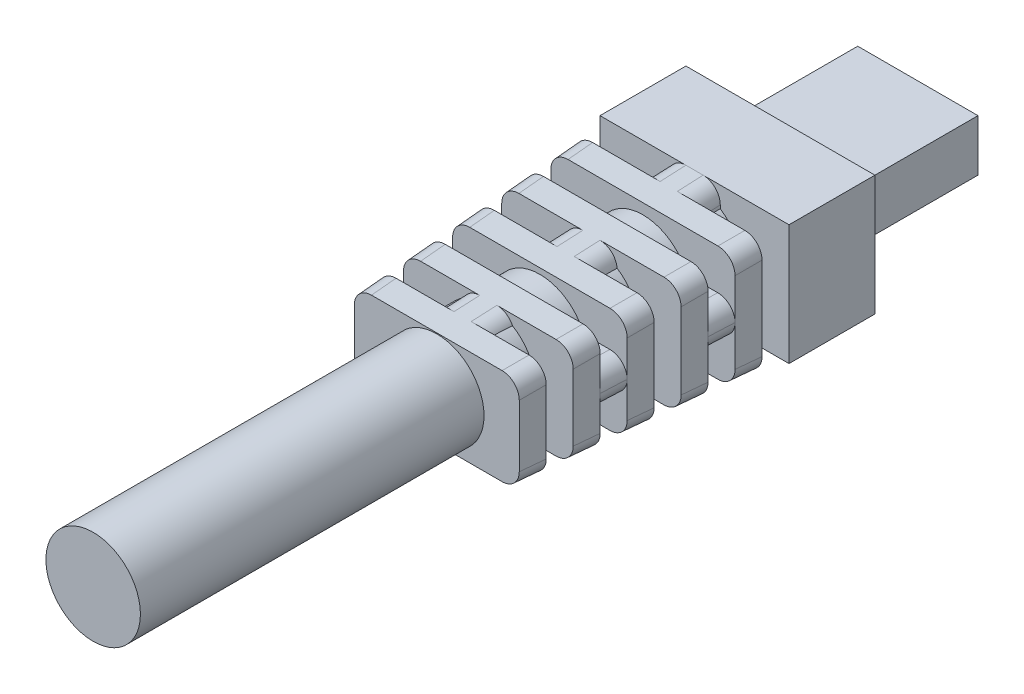
SolidWorks part; units mm, degrees
material "ПВХ 0.007 Смягченный"
ref_plane "Front" through (0, 0, 0) normal (0, 0, 1) x (1, 0, 0)
ref_plane "Top" through (0, 0, 0) normal (0, 1, 0) x (1, 0, 0)
ref_plane "Right" through (0, 0, 0) normal (1, 0, 0) x (0, 0, -1)
sketch "Эскиз1" plane through (0, 0, 0) normal (0, 0, 1) x (1, 0, 0)
  line L1 (0, 0) -> (-7, 0)
  line L2 (0, 0) -> (0, 3)
  line L3 (0, 3) -> (-7, 3)
  line L4 (-7, 0) -> (-7, 3)
  dimension "D1" = 7
  dimension "D2" = 3
extrude "Бобышка-Вытянуть1" add sketch "Эскиз1" along normal blind 8
sketch "Эскиз2" plane through (0, 0, 8) normal (0, 0, 1) x (1, 0, 0)
  line L0 (-7, 3) -> (-7, 0) construction
  line L1 (-9, -2) -> (2, -2)
  line L2 (-9, -2) -> (-9, 5)
  line L3 (-9, 5) -> (2, 5)
  line L4 (2, -2) -> (2, 5)
  line L5 (0, 0) -> (0, 3) construction
  line L6 (0, 3) -> (-7, 3) construction
  line L7 (-7, 0) -> (0, 0) construction
  point P4 (-7, 1.5)
  point P7 (0, 1.5)
  point P10 (-3.5, 3)
  dimension "D1" = 2
  dimension "D2" = 2
  dimension "D3" = 2
  dimension "D4" = 2
extrude "Бобышка-Вытянуть2" add sketch "Эскиз2" along normal blind 5
sketch "Эскиз3" plane through (0, 0, 13) normal (0, 0, 1) x (1, 0, 0)
  line L1 (-9, -2) -> (2, -2)
  line L2 (-9, -2) -> (-9, 5)
  line L3 (-9, 5) -> (2, 5)
  line L4 (2, -2) -> (2, 5)
extrude "Бобышка-Вытянуть3" add sketch "Эскиз3" along normal blind 15
chamfer "Фаска1" distance 15 distance2 0.7 4 edges at (2, 1.5, 28) (-3.5, 5, 28) (-9, 1.5, 28) (-3.5, -2, 28) first distance on face at (2, 1.5, 18) first distance on face at (-3.5, 5, 18) first distance on face at (-9, 1.5, 18) first distance on face at (-3.5, -2, 18)
ref_plane "Плоскость1" through (-3.5, 0, 0) normal (-1, 0, 0) x (0, 0, 1)
sketch "Эскиз5" plane through (-9, 0, 0) normal (-1, 0, 0) x (0, 0, 1)
  line L0 (16, -2) -> (17.5, -2)
  line L1 (13, -2) -> (14.5, -2)
  line L2 (13, -2) -> (13, 0.5)
  line L3 (13, 0.5) -> (14.5, 0.5)
  line L4 (14.5, -2) -> (14.5, 0.5)
  line L5 (16, -2) -> (16, 0.5)
  line L6 (16, 0.5) -> (17.5, 0.5)
  line L7 (17.5, -2) -> (17.5, 0.5)
  line L8 (19, -2) -> (20.5, -2)
  line L9 (19, -2) -> (19, 0.5)
  line L10 (19, 0.5) -> (20.5, 0.5)
  line L11 (20.5, -2) -> (20.5, 0.5)
  line L12 (22, -2) -> (23.5, -2)
  line L13 (22, -2) -> (22, 0.5)
  line L14 (22, 0.5) -> (23.5, 0.5)
  line L15 (23.5, -2) -> (23.5, 0.5)
  line L16 (25, -2) -> (26.5, -2)
  line L17 (25, -2) -> (25, 0.5)
  line L18 (25, 0.5) -> (26.5, 0.5)
  line L19 (26.5, -2) -> (26.5, 0.5)
  line L20 (16, 2.5) -> (17.5, 2.5)
  line L21 (16, 2.5) -> (16, 5)
  line L22 (16, 5) -> (17.5, 5)
  line L23 (17.5, 2.5) -> (17.5, 5)
  line L24 (19, 2.5) -> (20.5, 2.5)
  line L25 (19, 2.5) -> (19, 5)
  line L26 (19, 5) -> (20.5, 5)
  line L27 (20.5, 2.5) -> (20.5, 5)
  line L28 (22, 2.5) -> (23.5, 2.5)
  line L29 (22, 2.5) -> (22, 5)
  line L30 (22, 5) -> (23.5, 5)
  line L31 (23.5, 2.5) -> (23.5, 5)
  line L32 (25, 2.5) -> (26.5, 2.5)
  line L33 (25, 2.5) -> (25, 5)
  line L34 (25, 5) -> (26.5, 5)
  line L35 (26.5, 2.5) -> (26.5, 5)
  line L36 (13, 2.5) -> (14.5, 2.5)
  line L37 (13, 2.5) -> (13, 5)
  line L38 (13, 5) -> (14.5, 5)
  line L39 (14.5, 2.5) -> (14.5, 5)
  dimension "D1" = 1.5
  dimension "D2" = 2.5
  dimension "D3" = 5
  dimension "D4" = 2
extrude "Вырез-Вытянуть1" cut sketch "Эскиз5" against normal blind 4
mirror "Зеркальное отражение1" about plane through (-3.5, 0, 0) normal (-1, 0, 0) of "Вырез-Вытянуть1"
fillet "Скругление1" radius 1 10 edges at (-8.335, -1.335, 27.25) (-8.475, -1.475, 24.25) (-8.615, -1.615, 21.25) (-8.755, -1.755, 18.25) (-8.895, -1.895, 15.25) (-8.335, 4.335, 27.25) (-8.475, 4.475, 24.25) (-8.615, 4.615, 21.25) (-8.755, 4.755, 18.25) (-8.895, 4.895, 15.25)
fillet "Скругление2" radius 1 10 edges at (1.895, -1.895, 15.25) (1.755, -1.755, 18.25) (1.615, -1.615, 21.25) (1.475, -1.475, 24.25) (1.335, -1.335, 27.25) (1.895, 4.895, 15.25) (1.755, 4.755, 18.25) (1.615, 4.615, 21.25) (1.475, 4.475, 24.25) (1.335, 4.335, 27.25)
sketch "Эскиз6" plane through (-9, 0, 0) normal (-1, 0, 0) x (0, 0, 1)
  line L0 (19, 0.5) -> (19, 2.5)
  line L1 (13, 0.5) -> (14.5, 0.5)
  line L2 (13, 0.5) -> (13, 2.5)
  line L3 (13, 2.5) -> (14.5, 2.5)
  line L4 (14.5, 0.5) -> (14.5, 2.5)
  line L5 (19, 0.5) -> (20.5, 0.5)
  line L6 (20.5, 0.5) -> (20.5, 2.5)
  line L7 (19, 2.5) -> (20.5, 2.5)
  line L8 (25, 0.5) -> (25, 2.5)
  line L9 (25, 0.5) -> (26.5, 0.5)
  line L10 (26.5, 0.5) -> (26.5, 2.5)
  line L11 (25, 2.5) -> (26.5, 2.5)
  dimension "D1" = 3
extrude "Вырез-Вытянуть2" cut sketch "Эскиз6" against normal blind 4
mirror "Зеркальное отражение4" about plane through (-3.5, 0, 0) normal (-1, 0, 0) of "Вырез-Вытянуть2"
ref_plane "Плоскость2" through (0, 1.5, 0) normal (0, -1, 0) x (-1, 0, 0)
sketch "Эскиз7" plane through (0, 5, 0) normal (0, 1, 0) x (1, 0, 0)
  line L0 (-5, -23.5) -> (-5, -22)
  line L1 (-5, -17.5) -> (-2, -17.5)
  line L2 (-5, -17.5) -> (-5, -16)
  line L3 (-5, -16) -> (-2, -16)
  line L4 (-2, -17.5) -> (-2, -16)
  line L5 (-5, -23.5) -> (-2, -23.5)
  line L6 (-2, -23.5) -> (-2, -22)
  line L7 (-5, -22) -> (-2, -22)
  dimension "D1" = 2
extrude "Вырез-Вытянуть3" cut sketch "Эскиз7" against normal blind 4
mirror "Зеркальное отражение5" about plane through (0, 1.5, 0) normal (0, -1, 0) of "Вырез-Вытянуть3"
fillet "Скругление3" radius 1 6 edges at (-2, -1.965, 13.75) (-5, -1.405, 25.75) (-2, -1.405, 25.75) (-5, -1.685, 19.75) (-2, -1.685, 19.75) (-5, -1.965, 13.75)
fillet "Скругление4" radius 1 4 edges at (1.545, 0.5, 22.75) (1.545, 2.5, 22.75) (1.825, 0.5, 16.75) (1.825, 2.5, 16.75)
fillet "Скругление5" radius 1 6 edges at (-2, 4.405, 25.75) (-5, 4.405, 25.75) (-2, 4.685, 19.75) (-5, 4.685, 19.75) (-2, 4.965, 13.75) (-5, 4.965, 13.75)
fillet "Скругление6" radius 1 4 edges at (-8.545, 2.5, 22.75) (-8.545, 0.5, 22.75) (-8.825, 2.5, 16.75) (-8.825, 0.5, 16.75)
sketch "Эскиз8" plane through (0, 0, 28) normal (0, 0, 1) x (1, 0, 0)
  line L0 (-3.5, 4.3) -> (-3.5, -1.3) construction
  line L1 (0.3011, 4.3) -> (-7.3011, 4.3) construction
  line L2 (-7.3011, -1.3) -> (0.3011, -1.3) construction
  line L3 (-8.3, 1.5) -> (1.3, 1.5) construction
  line L4 (-8.3, 3.3011) -> (-8.3, -0.3011) construction
  line L5 (1.3, -0.3011) -> (1.3, 3.3011) construction
  circle A0 centre (-3.5, 1.5) radius 2.75
  dimension "D1" = 5.5
extrude "Бобышка-Вытянуть4" add sketch "Эскиз8" along normal blind 20 and the other way blind 20
